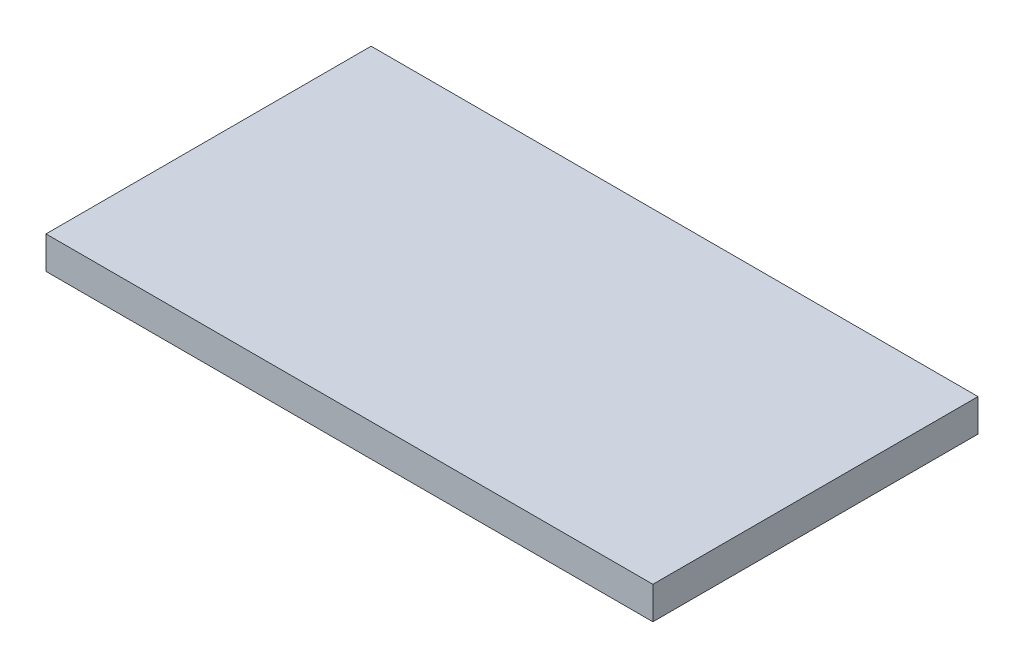
SolidWorks part; units mm, degrees
material "Maple"
ref_plane "Front Plane" through (0, 0, 0) normal (0, 0, 1) x (1, 0, 0)
ref_plane "Top Plane" through (0, 0, 0) normal (0, 1, 0) x (1, 0, 0)
ref_plane "Right Plane" through (0, 0, 0) normal (1, 0, 0) x (0, 0, -1)
sketch "Sketch1" plane through (0, 0, 0) normal (0, 1, 0) x (1, 0, 0)
  line L1 (0, 0) -> (1422.4, 0)
  line L2 (0, 0) -> (0, 762)
  line L3 (0, 762) -> (1422.4, 762)
  line L4 (1422.4, 0) -> (1422.4, 762)
  dimension "D1" = 762
  dimension "D2" = 1422.4
extrude "Boss-Extrude1" add sketch "Sketch1" along normal blind 76.2
sketch "Sketch3" plane through (0, 0, 0) normal (0, -1, 0) x (1, 0, 0)
  line L1 (101.6, -152.4) -> (203.2, -152.4)
  line L2 (101.6, -152.4) -> (101.6, -50.8)
  line L3 (101.6, -50.8) -> (203.2, -50.8)
  line L4 (203.2, -152.4) -> (203.2, -50.8)
  line L5 (101.6, -609.6) -> (203.2, -609.6)
  line L6 (101.6, -609.6) -> (101.6, -711.2)
  line L7 (101.6, -711.2) -> (203.2, -711.2)
  line L8 (203.2, -609.6) -> (203.2, -711.2)
  line L9 (1219.2, -50.8) -> (1320.8, -50.8)
  line L10 (1219.2, -50.8) -> (1219.2, -152.4)
  line L11 (1219.2, -152.4) -> (1320.8, -152.4)
  line L12 (1320.8, -50.8) -> (1320.8, -152.4)
  line L13 (1219.2, -609.6) -> (1320.8, -609.6)
  line L14 (1219.2, -609.6) -> (1219.2, -711.2)
  line L15 (1219.2, -711.2) -> (1320.8, -711.2)
  line L16 (1320.8, -609.6) -> (1320.8, -711.2)
  line L17 (0, 0) -> (1422.4, 0) construction
  line L18 (0, -762) -> (0, 0) construction
  line L19 (1422.4, -762) -> (0, -762) construction
  line L20 (1422.4, 0) -> (1422.4, -762) construction
  point P16 (136.1415, -119.0382)
  point P17 (373.3741, -322.7397)
  dimension "D1" = 101.6
  dimension "D2" = 101.6
  dimension "D3" = 101.6
  dimension "D4" = 101.6
  dimension "D5" = 101.6
  dimension "D6" = 101.6
  dimension "D7" = 101.6
  dimension "D8" = 101.6
  dimension "D9" = 50.8
  dimension "D10" = 101.6
  dimension "D11" = 101.6
  dimension "D12" = 50.8
  dimension "D13" = 50.8
  dimension "D14" = 101.6
  dimension "D15" = 101.6
  dimension "D16" = 50.8
